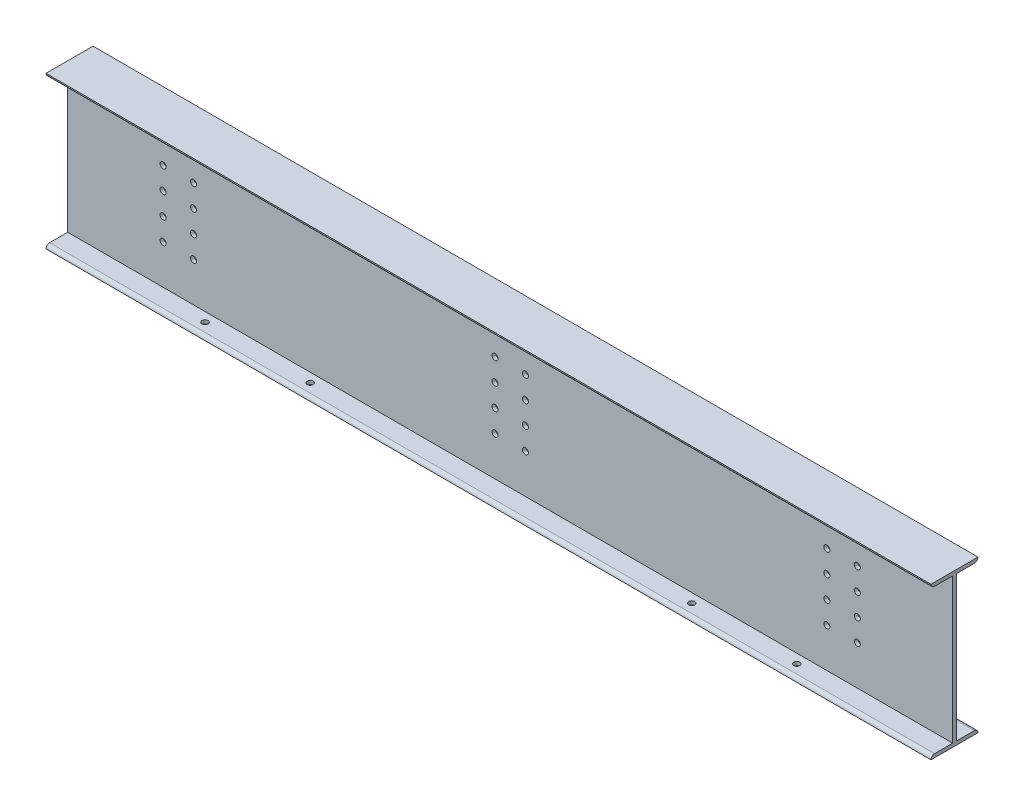
SolidWorks part; units mm, degrees
ref_plane "前视基准面" through (0, 0, 0) normal (0, 0, 1) x (1, 0, 0)
ref_plane "上视基准面" through (0, 0, 0) normal (0, 1, 0) x (1, 0, 0)
ref_plane "右视基准面" through (0, 0, 0) normal (1, 0, 0) x (0, 0, -1)
sketch "草图1" plane through (0, 0, 0) normal (0, 0, 1) x (1, 0, 0)
  line L1 (0, 550) -> (3200, 550)
  line L2 (0, 550) -> (0, 0)
  line L3 (0, 0) -> (3200, 0)
  line L4 (3200, 550) -> (3200, 0)
  dimension "D1" = 3200
  dimension "D2" = 550
extrude "拉伸1" add sketch "草图1" along normal blind 170
sketch "草图2" plane through (0, 0, 170) normal (0, 0, 1) x (1, 0, 0)
  line L2 (1600, -958.9103) -> (1600, 49041.0897) construction
  line L3 (0, 0) -> (3200, 0) construction
  circle A0 centre (345, 155) radius 11
  dimension "D1" = 1255
  dimension "D2" = 155
extrude "切除-拉伸1" cut sketch "草图2" against normal through all
pattern_linear "阵列(线性)1" count 4 spacing 80 along (0, 1, 0) count 2 spacing 110 along (1, 0, 0) of "切除-拉伸1"
pattern_linear "阵列(线性)2" count 3 spacing 1200 along (1, 0, 0) of "切除-拉伸1", "阵列(线性)1"
sketch "草图3" plane through (0, 0, 0) normal (0, -1, 0) x (1, 0, 0)
  line L2 (0, 170) -> (0, 0) construction
  circle A0 centre (530, 45) radius 11
  point P2 (0, 85)
  dimension "D1" = 40
  dimension "D2" = 530
extrude "切除-拉伸3" cut sketch "草图3" against normal blind 200
pattern_linear "阵列(线性)3" count 2 spacing 80 along (0, 0, 1) of "切除-拉伸3"
pattern_linear "阵列(线性)4" count 2 spacing 380 along (1, 0, 0) of "切除-拉伸3", "阵列(线性)3"
pattern_linear "阵列(线性)5" count 2 spacing 1760 along (1, 0, 0) of "切除-拉伸3", "阵列(线性)3", "阵列(线性)4"
sketch "草图4" plane through (0, 0, 0) normal (-1, 0, 0) x (0, 0, 1)
  line L0 (170, 550) -> (0, 550) construction
  line L2 (0, 550) -> (0, 0) construction
  line L3 (0, 537) -> (78.5, 537)
  line L4 (0, 537) -> (0, 13)
  line L5 (0, 13) -> (78.5, 13)
  line L6 (78.5, 537) -> (78.5, 13)
  line L7 (170, 0) -> (0, 0) construction
  line L8 (170, 550) -> (170, 0) construction
  line L9 (170, 537) -> (91.5, 537)
  line L10 (170, 537) -> (170, 13)
  line L11 (170, 13) -> (91.5, 13)
  line L12 (91.5, 537) -> (91.5, 13)
  point P2 (85, 550)
  dimension "D1" = 13
  dimension "D2" = 6.5
  dimension "D3" = 13
extrude "切除-拉伸4" cut sketch "草图4" against normal through all
fillet "圆角1" radius 13 1 edges at (1600, 13, 170)
fillet "圆角2" radius 13 1 edges at (1600, 13, 0)
fillet "圆角3" radius 13 1 edges at (1600, 537, 170)
fillet "圆角4" radius 13 1 edges at (1600, 537, 0)
